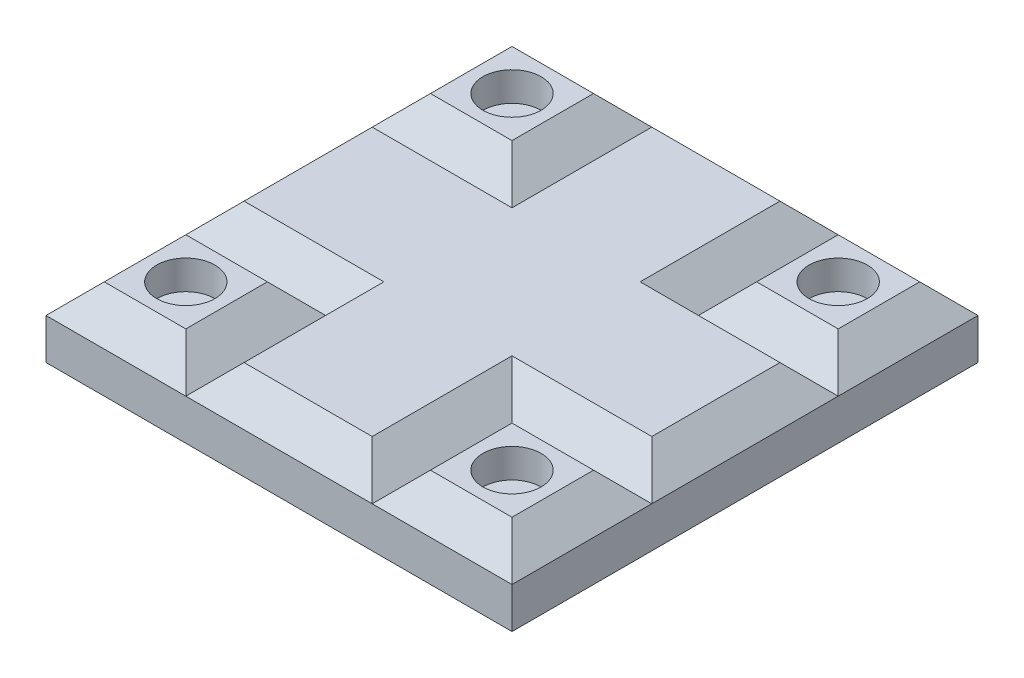
SolidWorks part; units mm, degrees
ref_plane "Front Plane" through (0, 0, 0) normal (0, 0, 1) x (1, 0, 0)
ref_plane "Top Plane" through (0, 0, 0) normal (0, 1, 0) x (1, 0, 0)
ref_plane "Right Plane" through (0, 0, 0) normal (1, 0, 0) x (0, 0, -1)
sketch "Sketch1" plane through (0, 0, 0) normal (0, 1, 0) x (1, 0, 0)
  line L1 (-20, -20) -> (20, -20)
  line L2 (-20, -20) -> (-20, 20)
  line L3 (-20, 20) -> (20, 20)
  line L4 (20, -20) -> (20, 20)
  line L5 (-20, -20) -> (20, 20) construction
  line L6 (-20, 20) -> (20, -20) construction
  point P0 (0, 0)
  dimension "D1" = 40
extrude "Boss-Extrude1" add sketch "Sketch1" along normal blind 6 contours L4 L3 L2 L1
sketch "Sketch2" plane through (0, 6, 0) normal (0, 1, 0) x (1, 0, 0)
  line L0 (20, 20) -> (8, 20)
  line L1 (-20, 20) -> (-8, 20)
  line L2 (-20, 20) -> (-20, 8)
  line L3 (-20, 8) -> (-8, 8)
  line L4 (-8, 20) -> (-8, 8)
  line L5 (20, 20) -> (20, 8)
  line L6 (20, 8) -> (8, 8)
  line L7 (8, 20) -> (8, 8)
  line L8 (20, -20) -> (20, -8)
  line L9 (20, -20) -> (8, -20)
  line L10 (8, -20) -> (8, -8)
  line L11 (20, -8) -> (8, -8)
  line L12 (-20, -20) -> (-8, -20)
  line L13 (-20, -20) -> (-20, -8)
  line L14 (-20, -8) -> (-8, -8)
  line L15 (-8, -20) -> (-8, -8)
  point P20 (0, 0)
  dimension "D1" = 12
  dimension "D2" = 4
extrude "Cut-Extrude1" cut sketch "Sketch2" against normal blind 2.5
chamfer "Chamfer1" distance 2.5 angle 45 12 edges at (-20, 6, 0) (-14, 6, -8) (-8, 6, -14) (0, 6, -20) (8, 6, -14) (14, 6, -8) (20, 6, 0) (14, 6, 8) (8, 6, 14) (0, 6, 20) (-8, 6, 14) (-14, 6, 8)
sketch "Sketch3" plane through (0, 3.5, 0) normal (0, 1, 0) x (1, 0, 0)
  line L1 (-20, -8) -> (-8, -8)
  line L2 (-20, -8) -> (-20, -20)
  line L3 (-20, -20) -> (-8, -20)
  line L4 (-8, -8) -> (-8, -20)
extrude "Boss-Extrude2" add sketch "Sketch3" along normal blind 2.5
chamfer "Chamfer2" distance 2.5 angle 45 4 edges at (-14, 6, 8) (-8, 6, 14) (-14, 6, 20) (-20, 6, 14)
pattern_circular "CirPattern1" count 4 every 90 about axis through (0, 6, 0) along (0, 1, 0) of "Boss-Extrude2", "Chamfer2"
sketch "Sketch4" plane through (0, 6, 0) normal (0, 1, 0) x (1, 0, 0)
  line L0 (-17.5, -10.5) -> (-10.5, -17.5) construction
  circle A0 centre (-14, -14) radius 2.5
extrude "Cut-Extrude2" cut sketch "Sketch4" against normal blind 2.5
pattern_circular "CirPattern2" count 4 every 90 about axis through (0, 6, 0) along (0, 1, 0) of "Cut-Extrude2"
